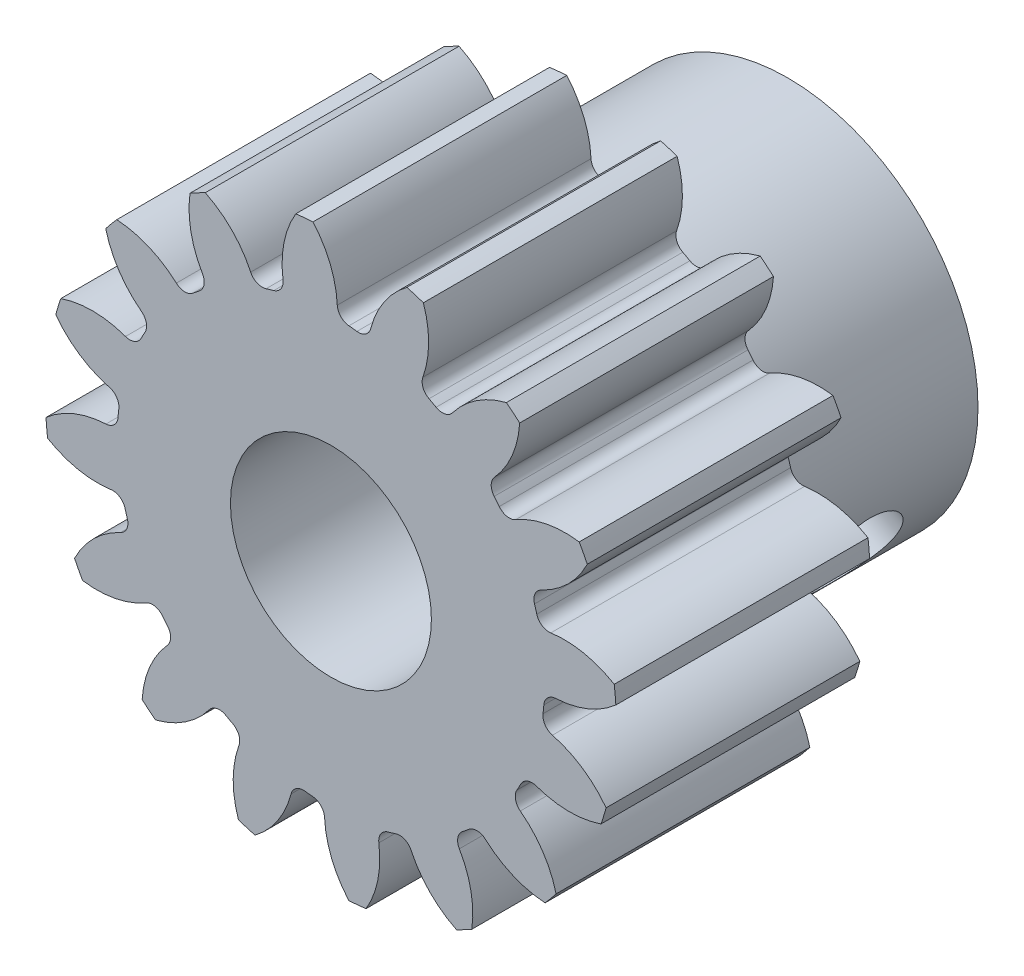
SolidWorks part; units mm, degrees
ref_plane "Front" through (0, 0, 0) normal (0, 0, 1) x (1, 0, 0)
ref_plane "Top" through (0, 0, 0) normal (0, 1, 0) x (1, 0, 0)
ref_plane "Right" through (0, 0, 0) normal (1, 0, 0) x (0, 0, -1)
sketch "Sketch3" plane through (0, 0, 0) normal (0, 0, 1) x (1, 0, 0)
  circle A0 centre (0, 0) radius 7.1438
  dimension "od" = 14.2875
extrude "gearBody" add sketch "Sketch3" along normal blind 6.35
sketch "Sketch2" plane through (0, 0, 0) normal (0, 0, 1) x (1, 0, 0)
  line L0 (0, 0) -> (5.5128, 2.2835) construction
  line L1 (7.1877, -2.4303) -> (0, 0) construction
  line L2 (0, 0) -> (36.3143, 0) construction
  line L3 (6.35, -0.0143) -> (6.2181, -1.2875) construction
  line L5 (6.284, -0.6509) -> (0, 0) construction
  line L7 (0, 0) -> (5.967, 0) construction
  arc A0 (5.9658, -0.1198) -> (5.8637, -1.1056) centre (0, 0) ccw construction
  arc A1 (7.1296, 0.4486) -> (6.8863, -1.9004) centre (0, 0) ccw construction
  arc A2 (6.35, -0.0143) -> (6.2181, -1.2875) centre (0, 0) ccw construction
  arc A3 (5.3069, -0.6512) -> (5.3277, -0.4504) centre (0, 0) ccw
  arc A4 (7.1877, -2.4303) -> (5.5428, -0.998) centre (4.9278, -3.365) ccw
  arc A5 (7.1877, -2.4303) -> (7.5332, 0.9055) centre (0, 0) ccw
  arc A6 (7.5332, 0.9055) -> (5.6297, -0.1593) centre (5.5128, 2.2835) cw
  arc A7 (5.3277, -0.4504) -> (5.6297, -0.1593) centre (5.6449, -0.4772) cw
  arc A8 (5.5428, -0.998) -> (5.3069, -0.6512) centre (5.6228, -0.6899) cw
  point P6 (7.5332, 0.9055)
  point P22 (7.1877, -2.4303)
  dimension "baseDia" = 11.9341
  dimension "od" = 14.2875
  dimension "pd" = 12.7
  dimension "rd" = 10.6934
  dimension "rFillet" = 0.3183
  dimension "pointX" = 7.5332
  dimension "pointY" = 0.9055
  dimension "CTT" = 1.2732
  dimension "flankCenterAngle" = 22.5
extrude "toothCut" cut sketch "Sketch2" along normal through all
pattern_circular "CirPattern1" count 16 over 360 about axis through (0, 0, 6.35) along (0, 0, -1) of "toothCut"
ref_axis "toothSpace" through (0, 0, 0) along (0.9947, -0.103, 0)
ref_axis "Axis2" through (6.8256, -2.1081, 0) along (-0.9555, 0.2951, 0)
sketch "hub1Dia" plane through (0, 0, 0) normal (0, 0, -1) x (-1, 0, 0)
  circle A0 centre (0, 0) radius 4.7625
  dimension "hub1Dia" = 9.525
extrude "hub1" add sketch "hub1Dia" along normal blind 5.08
sketch "hub2Dia" plane through (0, 0, 6.35) normal (0, 0, 1) x (1, 0, 0)
  circle A0 centre (0, 0) radius 12.7
  dimension "hub2dia" = 25.4
sketch "boreDia" plane through (0, 0, 0) normal (0, 0, 1) x (1, 0, 0)
  circle A0 centre (0, 0) radius 2.5146
  dimension "boreDia" = 5.0292
extrude "bore" cut sketch "boreDia" against normal mid plane 25400
sketch "kwy1sketch" plane through (0, 0, 0) normal (0, 0, 1) x (1, 0, 0)
  line L0 (-4.5261, 2.4486) -> (0, 0) construction
  line L1 (30.595, -2.1127) -> (18.5087, -24.4528)
  line L2 (18.5087, -24.4528) -> (-9.4165, -9.3451)
  line L3 (30.595, -2.1127) -> (2.6697, 12.9951)
  line L4 (-9.4165, -9.3451) -> (0, 0)
  line L5 (0, 0) -> (2.6697, 12.9951)
  line L6 (0, 0) -> (5.3182, -0.5509) construction
  line L7 (24.5518, -13.2828) -> (0, 0) construction
  arc A7 (5.3069, -0.6512) -> (5.3277, -0.4504) centre (0, 0) ccw construction
  point P9 (24.5518, -13.2828)
  point P13 (-0.755, 0.4085)
  dimension "kwy1width" = 25.4
  dimension "kwy1depth" = 27.9146
  dimension "kwy1angle" = 22.5
  dimension "kwy1Depth2" = 31.75
sketch "kwy2sketch" plane through (0, 0, 0) normal (0, 0, 1) x (1, 0, 0)
  line L0 (5.3182, -0.5509) -> (0, 0) construction
  line L1 (0, 0) -> (-3.4081, -1.0151) construction
  line L2 (23.1278, 20.14) -> (30.3784, -4.2031)
  line L3 (30.3784, -4.2031) -> (-0.0505, -13.2664)
  line L4 (23.1278, 20.14) -> (-7.3011, 11.0767)
  line L5 (-0.0505, -13.2664) -> (0, 0)
  line L6 (0, 0) -> (-7.3011, 11.0767)
  arc A2 (5.3069, -0.6512) -> (5.3277, -0.4504) centre (0, 0) ccw construction
  point P10 (26.7531, 7.9684)
  dimension "kwy2angle" = 22.5
  dimension "kwy2Width" = 25.4
  dimension "kwy2depth" = 27.9146
  dimension "kwy2Depth2" = 31.75
sketch "kwy3sketch" plane through (0, 0, 0) normal (0, 0, 1) x (1, 0, 0)
  line L0 (5.3182, -0.5509) -> (0, 0) construction
  line L1 (0, 0) -> (-1.2242, -2.2627) construction
  line L2 (2.1127, 30.595) -> (24.4528, 18.5087)
  line L3 (24.4528, 18.5087) -> (9.3451, -9.4165)
  line L4 (2.1127, 30.595) -> (-12.9951, 2.6697)
  line L5 (9.3451, -9.4165) -> (0, 0)
  line L6 (-12.9951, 2.6697) -> (0, 0)
  point P10 (13.2828, 24.5518)
  dimension "kwy3angle" = 67.5
  dimension "kwy3depth" = 27.9146
  dimension "kwy3width" = 25.4
  dimension "kwy3Depth2" = 31.75
sketch "kwy4sketch" plane through (0, 0, 0) normal (0, 0, 1) x (1, 0, 0)
  line L0 (5.3182, -0.5509) -> (0, 0) construction
  line L1 (0, 0) -> (0.5742, -1.9279) construction
  line L2 (4.2031, 30.3784) -> (-20.14, 23.1278)
  line L3 (-20.14, 23.1278) -> (-11.0767, -7.3011)
  line L4 (-11.0767, -7.3011) -> (0, 0)
  line L5 (13.2664, -0.0505) -> (0, 0)
  line L6 (4.2031, 30.3784) -> (13.2664, -0.0505)
  point P15 (-7.9684, 26.7531)
  dimension "kwy4angle" = 112.5
  dimension "kwy4depth" = 27.9146
  dimension "kwy4width" = 25.4
  dimension "kwy4Depth2" = 31.75
sketch "kwy5sketch" plane through (0, 0, 0) normal (0, 0, 1) x (1, 0, 0)
  line L0 (5.3182, -0.5509) -> (0, 0) construction
  line L1 (0, 0) -> (1.5195, -0.8221) construction
  line L2 (-18.5087, 24.4528) -> (-30.595, 2.1127)
  line L3 (-30.595, 2.1127) -> (-2.6697, -12.9951)
  line L4 (-18.5087, 24.4528) -> (9.4165, 9.3451)
  line L5 (-2.6697, -12.9951) -> (0, 0)
  line L6 (9.4165, 9.3451) -> (0, 0)
  point P10 (-24.5518, 13.2828)
  dimension "kwy5width" = 25.4
  dimension "kwy5depth" = 27.9146
  dimension "kwy5angle" = 157.5
  dimension "kwy5Depth2" = 31.75
sketch "kwy6sketch" plane through (0, 0, 0) normal (0, 0, 1) x (1, 0, 0)
  line L0 (5.3182, -0.5509) -> (0, 0) construction
  line L1 (0, 0) -> (1.6544, 0.4928) construction
  line L2 (-30.3784, 4.2031) -> (-23.1278, -20.14)
  line L3 (-23.1278, -20.14) -> (7.3011, -11.0767)
  line L4 (-30.3784, 4.2031) -> (0.0505, 13.2664)
  line L5 (7.3011, -11.0767) -> (0, 0)
  line L6 (0.0505, 13.2664) -> (0, 0)
  point P10 (-26.7531, -7.9684)
  dimension "kwy6angle" = 202.5
  dimension "kwy6width" = 25.4
  dimension "kwy6depth" = 27.9146
  dimension "kwy6Depth2" = 31.75
sketch "kwy7sketch" plane through (0, 0, 0) normal (0, 0, 1) x (1, 0, 0)
  line L0 (5.3182, -0.5509) -> (0, 0) construction
  line L1 (0, 0) -> (0.9202, 1.701) construction
  line L2 (-24.4528, -18.5087) -> (-2.1127, -30.595)
  line L3 (-24.4528, -18.5087) -> (-9.3451, 9.4165)
  line L4 (-2.1127, -30.595) -> (12.9951, -2.6697)
  line L5 (-9.3451, 9.4165) -> (0, 0)
  line L6 (12.9951, -2.6697) -> (0, 0)
  point P10 (-13.2828, -24.5518)
  dimension "kwy7angle" = 67.5
  dimension "kwy7width" = 25.4
  dimension "kwy7depth" = 27.9146
  dimension "kwy7angle1" = 247.5
  dimension "kwy7Depth2" = 31.75
sketch "kwy8sketch" plane through (0, 0, 0) normal (0, 0, 1) x (1, 0, 0)
  line L0 (5.3182, -0.5509) -> (0, 0) construction
  line L1 (0, 0) -> (-0.4905, 1.6467) construction
  line L2 (-4.2031, -30.3784) -> (20.14, -23.1278)
  line L3 (20.14, -23.1278) -> (11.0767, 7.3011)
  line L4 (-4.2031, -30.3784) -> (-13.2664, 0.0505)
  line L5 (11.0767, 7.3011) -> (0, 0)
  line L6 (-13.2664, 0.0505) -> (0, 0)
  point P10 (7.9684, -26.7531)
  dimension "kwy8angle" = 292.5
  dimension "kwy8width" = 25.4
  dimension "kwy8depth" = 27.9146
  dimension "kwy8Depth2" = 31.75
sketch "centerLine" plane through (0, 0, 0) normal (0, 1, 0) x (1, 0, 0)
  line L0 (0, 36.4807) -> (0, -59.6309) construction
ref_plane "CB1plane" through (0, 0, -5.08) normal (0, 0, -1) x (-1, 0, 0)
sketch "CB1diameter" plane through (0, 0, -5.08) normal (0, 0, -1) x (-1, 0, 0)
  circle A0 centre (0, 0) radius 12.7
  dimension "CB1diameter" = 25.4
ref_plane "CB2plane" through (0, 0, 6.35) normal (0, 0, 1) x (1, 0, 0)
sketch "CB2diameter" plane through (0, 0, 6.35) normal (0, 0, 1) x (1, 0, 0)
  circle A0 centre (0, 0) radius 12.7
  dimension "CB2diameter" = 25.4
ref_axis "Axis1" through (0, 0, 50) along (0, 0, -1)
hole_wizard "ss1Hub1" positions "ss1TriangleH1" profile "ss1SketchH1" tap size "5/8-11" standard "Ansi Inch"
sketch3d "ss1TriangleH1"
  line L0 (0, 0, 0) -> (4.1888, -2.2662, -2.54) construction
  line L1 (4.1888, -2.2662, -2.54) -> (4.1888, -2.2662, 0) construction
  line L2 (4.1888, -2.2662, 0) -> (0, 0, 0) construction
  line L7 (4.1888, -2.2662, 0) -> (0, 0, 0) construction
  line L21 (2.8305, -0.2932, 0) -> (0, 0, 0) construction
  line L22 (0, 0, 0) -> (5.3182, -0.5509, 0) construction
  circle A0 centre (0, 0, 0) radius 4.7625 construction
  point P1 (4.1888, -2.2662, -2.54)
  point P10 (0, 0, -4.7625)
  dimension "ss1HeightH1" = 2.54
  dimension "ss1AngleH1" = 22.5
sketch "ss1SketchH1" plane through (4.1888, -2.2662, -2.54) normal (0, 0, 1) x (0.4758, 0.8795, 0)
  line L0 (0, 0) -> (0, 5.4462)
  line L1 (0, 5.4462) -> (1.1379, 4.7625)
  line L2 (1.1379, 4.7625) -> (1.1379, 0)
  line L5 (1.1379, 0) -> (0, 0)
  line L10 (0, 5.4462) -> (-1.1379, 4.7625) construction
  line L11 (0, -6.35) -> (0, 107.95) construction
  dimension "ss1TapDiamH1" = 2.2758
  dimension "Tap Drill Depth" = 4.7625
  dimension "Drill Angle" = 118
cosmetic thread "ss1ThreadH1" parameters "D1"=9.5249, "ss1ThreadDiamH1"=2.8448
sketch3d "3DSketch1" plane through (0, 0, 0) normal (0, 0, 1) x (1, 0, 0)
